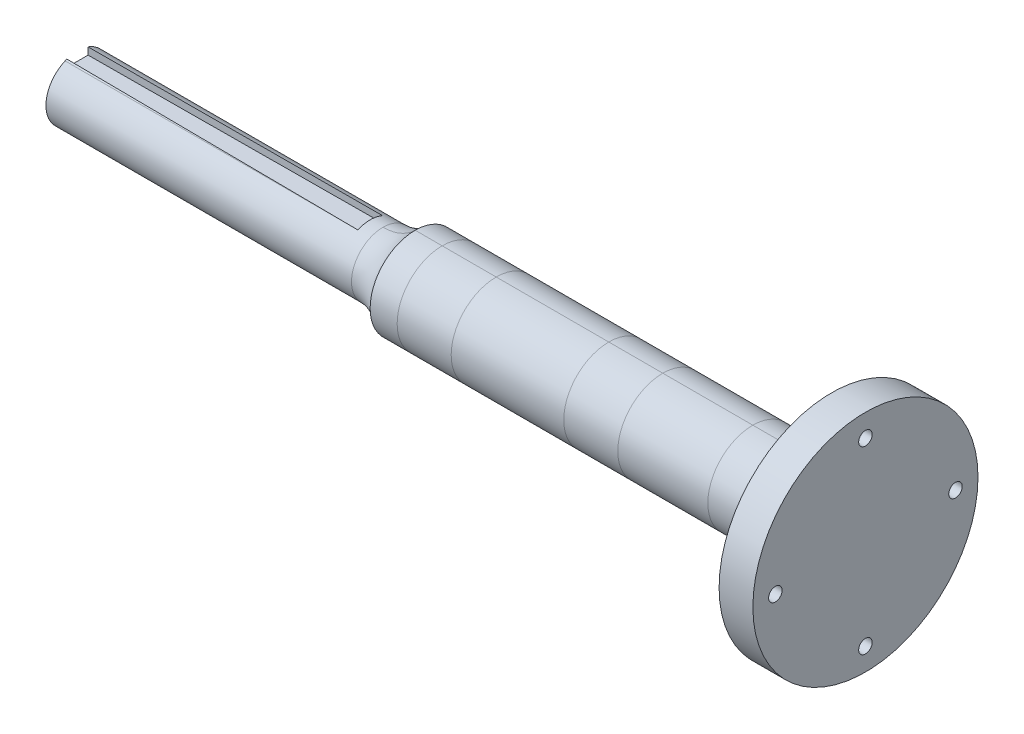
SolidWorks part; units mm, degrees
material "1023 Carbon Steel Sheet (SS)"
ref_plane "Front Plane" through (0, 0, 0) normal (0, 0, 1) x (1, 0, 0)
ref_plane "Top Plane" through (0, 0, 0) normal (0, 1, 0) x (1, 0, 0)
ref_plane "Right Plane" through (0, 0, 0) normal (1, 0, 0) x (0, 0, -1)
sketch "Sketch1" plane through (0, 0, 0) normal (1, 0, 0) x (0, 0, -1)
  circle A0 centre (0, 0) radius 10
  dimension "D1" = 20
extrude "Boss-Extrude1" add sketch "Sketch1" against normal blind 175
sketch "Sketch2" plane through (0, 0, 0) normal (0, 1, 0) x (1, 0, 0)
  line L0 (-94, -10) -> (-94, 10)
  line L1 (-175, -10) -> (0, -10) construction
  line L2 (0, 10) -> (-175, 10) construction
  line L3 (-45, -10) -> (-45, 10)
  line L5 (-175, -10) -> (0, -10) construction
  line L6 (0, 10) -> (-175, 10) construction
  line L7 (-82, -10) -> (-82, 10)
  line L8 (-57, -10) -> (-57, 10)
  line L10 (-25, 10) -> (-25, -10)
  line L11 (0, 10) -> (-175, 10) construction
  line L13 (-10, 10) -> (-10, -10)
  line L14 (-175, -10) -> (0, -10) construction
  line L15 (0, -10) -> (0, 10) construction
  line L16 (0, 0) -> (-175, 0)
  line L17 (-175, 10) -> (-175, -10) construction
  dimension "D1" = 45
  dimension "D2" = 15
  dimension "D3" = 25
  dimension "D4" = 12
  dimension "D5" = 12
  dimension "D6" = 10
split line "Split Line1"
sketch "Sketch3" plane through (-175, 0, 0) normal (-1, 0, 0) x (0, 0, 1)
  circle A0 centre (0, 0) radius 7
  circle A1 centre (0, 0) radius 10
  dimension "D1" = 14
  dimension "D2" = 20
extrude "Cut-Extrude1" cut sketch "Sketch3" against normal blind 75
fillet "Fillet1" radius 10 1 edges at (-100, 0, 7)
sketch "Sketch4" plane through (0, 0, 0) normal (1, 0, 0) x (0, 0, -1)
  circle A0 centre (0, 0) radius 25
  circle A1 centre (0, 0) radius 20 construction
  circle A3 centre (0, 20) radius 1.5
  circle A4 centre (20, 0) radius 1.5
  circle A5 centre (0, -20) radius 1.5
  circle A6 centre (-20, 0) radius 1.5
  point P15 (0, 0)
  dimension "D1" = 50
  dimension "D2" = 40
  dimension "D3" = 3
  dimension "D4" = 4
extrude "Boss-Extrude2" add sketch "Sketch4" against normal blind 7.5
fillet "Fillet3" radius 2.5 2 edges at (-7.5, 0, -10) (-7.5, 0, 10)
ref_plane "Plane1" through (0, 7, 0) normal (0, 1, 0) x (1, 0, 0)
sketch "Sketch9" plane through (0, 7, 0) normal (0, 1, 0) x (1, 0, 0)
  line L0 (-175, 0) -> (-110, 0) construction
  line L3 (-175, 7) -> (-107.1414, 7) construction
  line L4 (-175, -2.35) -> (-175, 2.35)
  line L5 (-175, 2.35) -> (-110, 2.75)
  line L6 (-110, 2.75) -> (-110, -2.75)
  line L7 (-175, -2.35) -> (-110, -2.75)
  line L9 (-175, 7) -> (-175, -7) construction
  dimension "D1" = 65
  dimension "D2" = 2.35
  dimension "D3" = 2.75
extrude "Cut-Extrude2" cut sketch "Sketch9" against normal blind 2 contours L5 L6 L7 L4
